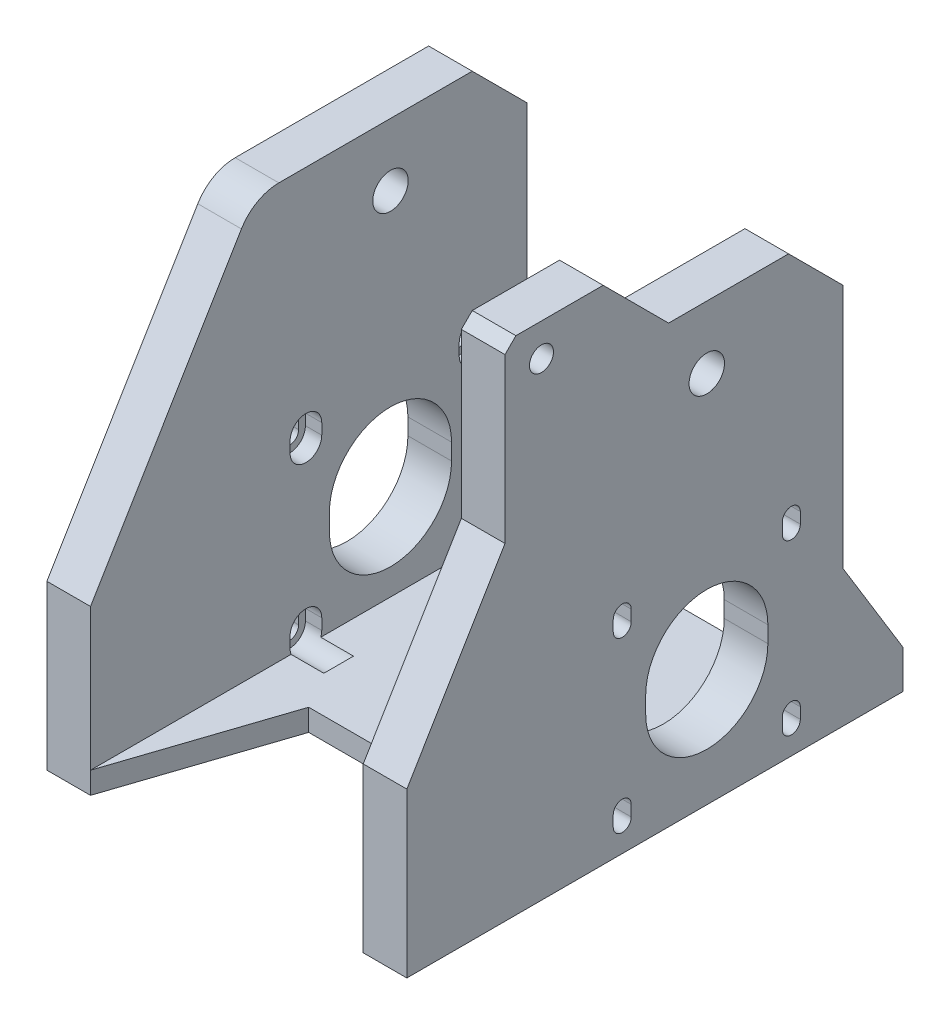
SolidWorks part; units mm, degrees
ref_plane "前视基准面" through (0, 0, 0) normal (0, 0, 1) x (1, 0, 0)
ref_plane "上视基准面" through (0, 0, 0) normal (0, 1, 0) x (1, 0, 0)
ref_plane "右视基准面" through (0, 0, 0) normal (1, 0, 0) x (0, 0, -1)
other "Configuration Table"
sketch "草图1" plane through (0, 0, 0) normal (0, 0, 1) x (1, 0, 0)
  line L0 (0, 21.7014) -> (0, -12.4863) construction
  line L1 (-15.1126, 0) -> (18.2457, 0) construction
  line L2 (33, 0) -> (-33, 0)
  line L3 (-33, 0) -> (-33, 80)
  line L4 (-33, 80) -> (-25, 80)
  line L5 (-25, 80) -> (-25, 4)
  line L6 (-25, 4) -> (25, 4)
  line L7 (25, 80) -> (25, 4)
  line L8 (33, 80) -> (25, 80)
  line L9 (33, 0) -> (33, 80)
  point P12 (0, 4)
  point P15 (0, 0)
  dimension "D1" = 25
  dimension "D2" = 4
  dimension "D3" = 8
  dimension "D4" = 80
extrude "凸台-拉伸1" add sketch "草图1" along normal blind 50
sketch "草图3" plane through (0, 0, 0) normal (0, -1, 0) x (1, 0, 0)
  line L0 (-33, 50) -> (33, 0) construction
  line L1 (-33, 0) -> (33, 50) construction
  circle A0 centre (0, 25) radius 6
  dimension "D1" = 12
extrude "切除-拉伸1" cut sketch "草图3" against normal blind 50
sketch "草图4" plane through (0, 0, 0) normal (0, -1, 0) x (1, 0, 0)
  line L0 (0, 25) -> (-13.581, 11.419) construction
  line L1 (0, 25) -> (-32.7293, 25) construction
  circle A0 centre (0, 25) radius 15 construction
  circle A1 centre (0, 40) radius 1.8
  circle A2 centre (15, 25) radius 1.8
  circle A3 centre (0, 10) radius 1.8
  circle A4 centre (-15, 25) radius 1.8
  point P14 (0, 25)
  dimension "D1" = 30
  dimension "D2" = 3.6
  dimension "D4" = 45
  dimension "D3" = 4
extrude "切除-拉伸2" cut sketch "草图4" against normal blind 28
chamfer "倒角1" distance 1.5 angle 45 4 edges at (-13.2, 4, 25) (16.8, 4, 25) (1.8, 4, 40) (1.8, 4, 10)
sketch "草图6" plane through (-33, 0, 0) normal (-1, 0, 0) x (0, 0, 1)
  line L0 (25, 8.6654) -> (25, 80.2189) construction
  line L2 (50, 0) -> (0, 0) construction
  line L3 (25, 20) -> (25, 23) construction
  line L4 (13.8, 20) -> (13.8, 23)
  line L5 (36.2, 20) -> (36.2, 23)
  line L6 (9.5, 38) -> (9.5, 36) construction
  line L7 (9.5, 6) -> (40.5, 6) construction
  line L8 (9.5, 6) -> (9.5, 37) construction
  line L9 (9.5, 37) -> (40.5, 37) construction
  line L10 (40.5, 6) -> (40.5, 37) construction
  line L11 (9.5, 6) -> (40.5, 37) construction
  line L12 (9.5, 37) -> (40.5, 6) construction
  line L13 (11.15, 38) -> (11.15, 36)
  line L14 (7.85, 38) -> (7.85, 36)
  line L15 (40.5, 38) -> (40.5, 36) construction
  line L16 (38.85, 38) -> (38.85, 36)
  line L17 (42.15, 38) -> (42.15, 36)
  line L18 (21.7321, 21.5) -> (30.7815, 21.5) construction
  line L19 (9.5, 5) -> (9.5, 7) construction
  line L20 (11.15, 5) -> (11.15, 7)
  line L21 (7.85, 5) -> (7.85, 7)
  line L22 (40.5, 5) -> (40.5, 7) construction
  line L23 (38.85, 5) -> (38.85, 7)
  line L24 (42.15, 5) -> (42.15, 7)
  arc A1 (13.8, 20) -> (36.2, 20) centre (25, 20) ccw
  arc A2 (36.2, 23) -> (13.8, 23) centre (25, 23) ccw
  arc A3 (11.15, 38) -> (7.85, 38) centre (9.5, 38) ccw
  arc A4 (7.85, 36) -> (11.15, 36) centre (9.5, 36) ccw
  arc A5 (38.85, 38) -> (42.15, 38) centre (40.5, 38) cw
  arc A6 (42.15, 36) -> (38.85, 36) centre (40.5, 36) cw
  arc A7 (11.15, 5) -> (7.85, 5) centre (9.5, 5) cw
  arc A8 (7.85, 7) -> (11.15, 7) centre (9.5, 7) cw
  arc A9 (38.85, 5) -> (42.15, 5) centre (40.5, 5) ccw
  arc A10 (42.15, 7) -> (38.85, 7) centre (40.5, 7) ccw
  point P2 (25, 21.5)
  point P6 (25, 21.5)
  point P18 (9.5, 37)
  point P26 (40.5, 37)
  point P34 (9.5, 6)
  point P41 (40.5, 6)
  dimension "D1" = 3
  dimension "D5" = 2
  dimension "D2" = 20
  dimension "D3" = 31
  dimension "D4" = 31
extrude "切除-拉伸3" cut sketch "草图6" against normal blind 12
sketch "草图9" plane through (-33, 0, 0) normal (-1, 0, 0) x (0, 0, 1)
  line L0 (9.5, 38) -> (9.5, 36) construction
  line L1 (12.4, 38) -> (12.4, 36)
  line L2 (6.6, 38) -> (6.6, 36)
  line L3 (13.8, 21.5) -> (-5.2508, 21.5) construction
  line L5 (25, 34.2) -> (25, 40.029) construction
  line L6 (40.5, 38) -> (40.5, 36) construction
  line L7 (37.6, 38) -> (37.6, 36)
  line L8 (43.4, 38) -> (43.4, 36)
  line L9 (40.5, 5) -> (40.5, 7) construction
  line L10 (37.6, 5) -> (37.6, 7)
  line L11 (43.4, 5) -> (43.4, 7)
  line L12 (9.5, 5) -> (9.5, 7) construction
  line L13 (12.4, 5) -> (12.4, 7)
  line L14 (6.6, 5) -> (6.6, 7)
  arc A0 (12.4, 38) -> (6.6, 38) centre (9.5, 38) ccw
  arc A1 (6.6, 36) -> (12.4, 36) centre (9.5, 36) ccw
  arc A3 (37.6, 38) -> (43.4, 38) centre (40.5, 38) cw
  arc A4 (43.4, 36) -> (37.6, 36) centre (40.5, 36) cw
  arc A5 (37.6, 5) -> (43.4, 5) centre (40.5, 5) ccw
  arc A6 (43.4, 7) -> (37.6, 7) centre (40.5, 7) ccw
  arc A7 (12.4, 5) -> (6.6, 5) centre (9.5, 5) cw
  arc A8 (6.6, 7) -> (12.4, 7) centre (9.5, 7) cw
  point P4 (9.5, 37)
  point P14 (40.5, 37)
  point P22 (40.5, 6)
  point P29 (9.5, 6)
extrude "切除-拉伸4" cut sketch "草图9" against normal blind 9 from offset 5 offset against normal yes
mirror "镜向1" about plane through (0, 0, 0) normal (1, 0, 0) of "切除-拉伸4", "切除-拉伸3"
sketch "草图10" plane through (33, 0, 0) normal (1, 0, 0) x (0, 0, -1)
  line L0 (-36.2, 21.5) -> (-55.799, 21.5) construction
  line L2 (-25, 59.2334) -> (-25, 48.0334) construction
  circle A1 centre (-25, 68.5) radius 3.25
  dimension "D1" = 6.5
  dimension "D2" = 47
extrude "切除-拉伸5" cut sketch "草图10" against normal blind 80
chamfer "倒角2" distance 6 angle 45 1 edges at (29, 80, 50)
sketch "草图11" plane through (33, 0, 0) normal (1, 0, 0) x (0, 0, -1)
  line L0 (-37.1042, 68.5) -> (-55.8843, 68.5) construction
  line L1 (-32.2017, 72.6579) -> (-60.4497, 88.9669) construction
  line L7 (-50, 63.4456) -> (-50, 74)
  line L10 (-44, 80) -> (-44, 92)
  line L11 (-44, 80) -> (0, 80) construction
  line L12 (-44, 92) -> (-62, 92)
  line L13 (-62, 92) -> (-62, 74)
  line L15 (-50, 0) -> (-50, 74) construction
  line L16 (-50, 74) -> (-44, 80)
  line L17 (-62, 74) -> (-62, 54.7904)
  line L18 (-62, 54.7904) -> (-50, 54.7904)
  line L19 (-50, 54.7904) -> (-50, 63.4456)
  circle A0 centre (-55.3109, 86) radius 2.2
  point P7 (-25, 68.5)
  dimension "D3" = 4.4
  dimension "D1" = 30
  dimension "D2" = 35
  dimension "D4" = 0
  dimension "D6" = 12
  dimension "D7" = 12
extrude "凸台-拉伸2" add sketch "草图11" against normal blind 8
sketch "草图13" plane through (-33, 0, 0) normal (-1, 0, 0) x (0, 0, 1)
  line L0 (50, 80) -> (80, 30)
  line L1 (50, 0) -> (80, 0)
  line L2 (80, 0) -> (80, 30)
  line L3 (50, 80) -> (0, 80) construction
  line L4 (50, 80) -> (50, 0)
  dimension "D1" = 30
  dimension "D2" = 50
extrude "凸台-拉伸3" add sketch "草图13" against normal blind 8
mirror "镜向2" about plane through (0, 0, 0) normal (1, 0, 0) of "凸台-拉伸3"
sketch "草图14" plane through (0, 0, 0) normal (0, -1, 0) x (1, 0, 0)
  line L0 (-25, 80) -> (-15, 50)
  line L1 (-25, 50) -> (25, 50) construction
  line L2 (-15, 50) -> (-25, 50)
  line L3 (-25, 50) -> (-25, 80)
  dimension "D1" = 10
extrude "凸台-拉伸4" add sketch "草图14" against normal blind 4
mirror "镜向3" about plane through (0, 0, 0) normal (1, 0, 0) of "凸台-拉伸4"
sketch "草图16" plane through (-33, 0, 0) normal (-1, 0, 0) x (0, 0, 1)
  line L0 (0, 25) -> (-11, 7)
  line L1 (0, 80) -> (0, 0) construction
  line L2 (-11, 0) -> (0, 0)
  line L3 (0, 0) -> (0, 25)
  line L4 (-11, 7) -> (-11, 0)
  dimension "D1" = 7
  dimension "D2" = 25
  dimension "D3" = 11
extrude "凸台-拉伸6" add sketch "草图16" against normal blind 8
mirror "镜向5" about plane through (0, 0, 0) normal (1, 0, 0) of "凸台-拉伸6"
chamfer "倒角3" distance 10 angle 45 2 edges at (-29, 80, 0) (29, 80, 0)
chamfer "倒角4" distance 12 angle 45 1 edges at (29, 80, 44)
chamfer "倒角5" distance 2 angle 45 1 edges at (29, 92, 62)
fillet "圆角1" radius 8 1 edges at (-29, 80, 50)
sketch "草图17" plane through (25, 0, 0) normal (-1, 0, 0) x (0, 0, 1)
  circle A0 centre (55.3109, 86) radius 4.05
  dimension "D1" = 8.1
extrude "切除-拉伸6" cut sketch "草图17" against normal blind 3
fillet "圆角2" radius 0.5 1 edges at (25, 81.95, 55.3109)
